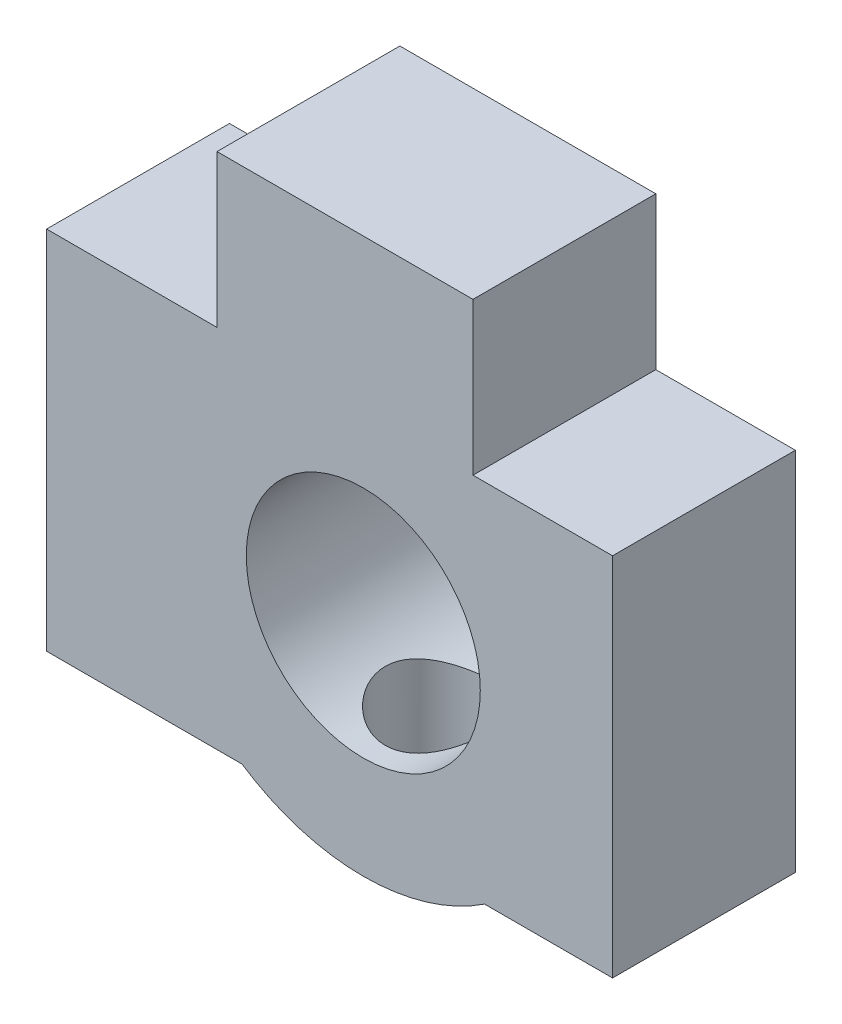
SolidWorks part; units mm, degrees
ref_plane "前视基准面" through (0, 0, 0) normal (0, 0, 1) x (1, 0, 0)
ref_plane "上视基准面" through (0, 0, 0) normal (0, 1, 0) x (1, 0, 0)
ref_plane "右视基准面" through (0, 0, 0) normal (1, 0, 0) x (0, 0, -1)
sketch "草图1" plane through (0, 0, 0) normal (0, 0, 1) x (1, 0, 0)
  line L0 (-3.3166, -5) -> (-8.6603, -5)
  line L1 (-8.6603, -5) -> (-8.6603, 5)
  line L2 (3.3166, -5) -> (6.8166, -5)
  line L4 (-4, 5) -> (-4, 9.1652)
  line L5 (6.8166, -5) -> (6.8166, 5)
  line L6 (6.8166, 5) -> (3, 5)
  line L7 (-4, 5) -> (-8.6603, 5)
  line L8 (3, 5) -> (3, 9.1652)
  line L9 (3, 9.1652) -> (-4, 9.1652)
  arc A1 (-3.3166, -5) -> (3.3166, -5) centre (0, 0) ccw
  circle A3 centre (0, 0) radius 3.2
  point P5 (0, 0)
  point P8 (0, 0)
  point P15 (0, 0)
  point P16 (0, 0)
extrude "凸台-拉伸1" add sketch "草图1" along normal blind 5
sketch "草图2" plane through (0, -5, 0) normal (0, -1, 0) x (1, 0, 0)
  circle A0 centre (0, 2.9) radius 1.5
extrude "切除-拉伸1" cut sketch "草图2" against normal blind 5 and the other way blind 5
